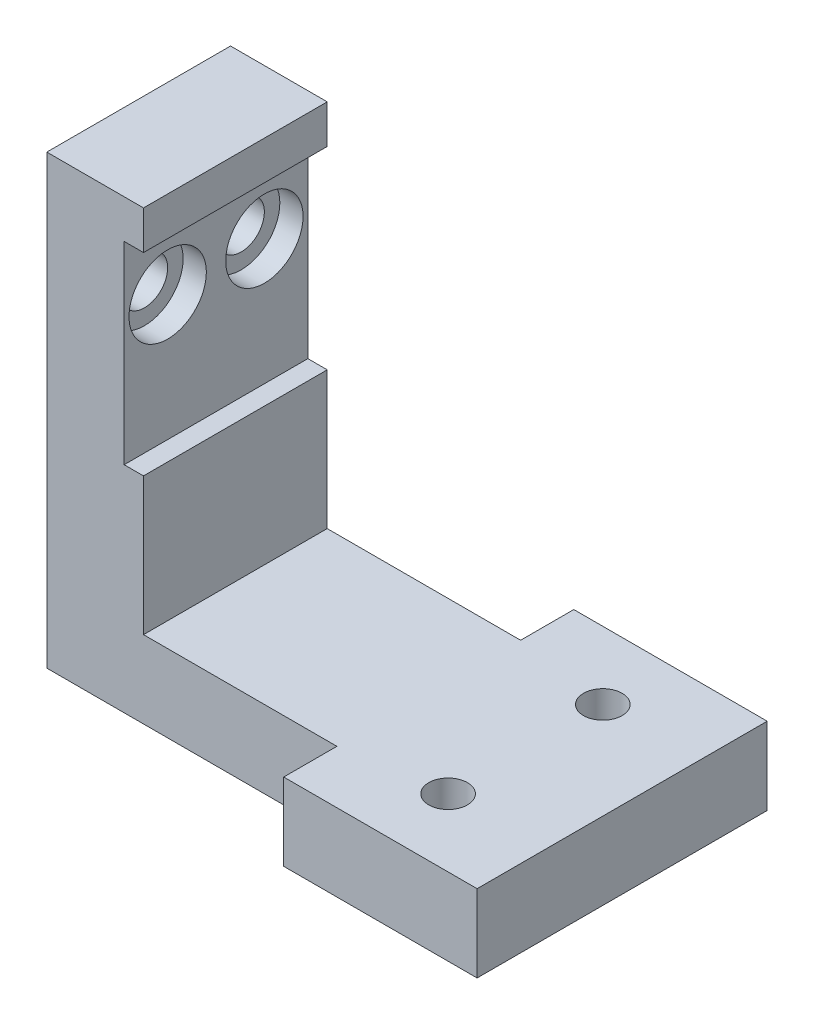
SolidWorks part; units mm, degrees
material "6061-T6 (SS)"
ref_plane "Front Plane" through (0, 0, 0) normal (0, 0, 1) x (1, 0, 0)
ref_plane "Top Plane" through (0, 0, 0) normal (0, 1, 0) x (1, 0, 0)
ref_plane "Right Plane" through (0, 0, 0) normal (1, 0, 0) x (0, 0, -1)
sketch "Sketch1" plane through (0, 0, 0) normal (0, 0, 1) x (1, 0, 0)
  line L0 (-15.4886, 8) -> (-17.5374, 8) construction
  line L9 (-17.5374, 3) -> (-17.5374, 13)
  line L10 (-21.5374, 0) -> (-21.5374, 15)
  line L11 (-21.5374, 15) -> (-16.5374, 15)
  line L12 (-16.5374, 15) -> (-16.5374, 13)
  line L17 (-12.4274, -4.11) -> (3.4626, -4.11)
  line L18 (3.4626, -4.11) -> (3.4626, -8.11)
  line L19 (3.4626, -8.11) -> (-13.4274, -8.11)
  line L20 (-17.5374, 13) -> (-16.5374, 13)
  line L21 (-17.5374, 3) -> (-16.5374, 3)
  line L22 (-16.5374, 3) -> (-16.5374, 0)
  line L23 (-21.5374, 0) -> (-21.5374, -8.11)
  line L24 (-21.5374, -8.11) -> (-13.4274, -8.11)
  line L25 (-16.5374, 0) -> (-16.5374, -4.11)
  line L26 (-16.5374, -4.11) -> (-12.4274, -4.11)
  line L29 (-12.4274, -4.11) -> (-10.0144, -4.11) construction
  point P15 (-17.5374, 8)
  point P21 (-12.4274, 0)
  dimension "D4" = 3
  dimension "D2" = 5
  dimension "D5" = 25
  dimension "D6" = 10
  dimension "D7" = 2
  dimension "D8" = 1
  dimension "D10" = 4
extrude "Boss-Extrude1" add sketch "Sketch1" along normal mid plane 9.5
sketch "Sketch2" plane through (-17.5374, 0, 0) normal (1, 0, 0) x (0, 0, -1)
  line L0 (-4.75, 8) -> (4.75, 8) construction
  line L1 (-4.75, 3) -> (-4.75, 13) construction
  line L2 (4.75, 3) -> (4.75, 13) construction
  line L3 (-4.75, 9.5) -> (4.75, 9.5) construction
  line L4 (0, 9.5) -> (0, 8) construction
  point P8 (-2.5, 9.5)
  point P11 (2.5, 9.5)
  dimension "D2" = 2.5
  dimension "D1" = 1.5
hole_wizard "M2 Clearance Hole1" positions "3DSketch1" profile "Sketch3" hole size "M2" standard "ANSI Metric" end condition through all
sketch3d "3DSketch1"
  point P0 (-17.5374, 9.5, 2.5)
  point P3 (-17.5374, 9.5, -2.5)
sketch "Sketch3" plane through (-17.5374, 9.5, 2.5) normal (0, 1, 0) x (0, 0, -1)
  line L0 (0, 0) -> (0, 4)
  line L1 (0, 4) -> (1.2, 4)
  line L2 (1.2, 4) -> (1.2, 0)
  line L5 (1.2, 0) -> (0, 0)
  line L11 (0, -6.35) -> (0, 107.95) construction
  dimension "Thru Hole Dia." = 2.4
  dimension "Thru Hole Depth" = 4
sketch "Sketch4" plane through (-17.5374, 0, 0) normal (1, 0, 0) x (0, 0, -1)
  circle A0 centre (-2.5, 9.5) radius 2
  circle A1 centre (2.5, 9.5) radius 2
  dimension "D1" = 4
  dimension "D2" = 4
extrude "Cut-Extrude1" cut sketch "Sketch4" against normal blind 1.2
sketch "Sketch5" plane through (0, -8.11, 0) normal (0, -1, 0) x (1, 0, 0)
  line L0 (3.4626, -7.5) -> (3.4626, 7.5)
  line L1 (3.4626, 4.75) -> (3.4626, -4.75) construction
  line L2 (3.4626, 7.5) -> (-6.5374, 7.5)
  line L3 (-6.5374, 7.5) -> (-6.5374, -7.5)
  line L4 (-6.5374, -7.5) -> (3.4626, -7.5)
  point P3 (3.4626, 0)
  dimension "D1" = 10
  dimension "D2" = 15
extrude "Boss-Extrude2" add sketch "Sketch5" against normal blind 4
sketch "Sketch6" plane through (0, -4.11, 0) normal (0, 1, 0) x (1, 0, 0)
  line L0 (3.4626, 0) -> (-6.5374, 0) construction
  line L1 (3.4626, 7.5) -> (3.4626, -7.5) construction
  line L3 (-1.5374, -7.5) -> (-1.5374, 7.5) construction
  line L4 (3.4626, -7.5) -> (-6.5374, -7.5) construction
  line L5 (-6.5374, 7.5) -> (3.4626, 7.5) construction
  point P12 (-1.5374, -4)
  point P13 (-1.5374, 0)
  point P14 (-1.5374, 4)
  dimension "D1" = 4
hole_wizard "Tap Drill for M2x0.4 Tap2" positions "3DSketch2" profile "Sketch7" hole size "M2x0.4" standard "ANSI Metric" end condition through all
sketch3d "3DSketch2"
  point P0 (-1.5374, -4.11, 4)
  point P3 (-1.5374, -4.11, -4)
sketch "Sketch7" plane through (-1.5374, -4.11, 4) normal (1, 0, 0) x (0, 0, 1)
  line L0 (0, 0) -> (0, 4)
  line L1 (0, 4) -> (1, 4)
  line L2 (1, 4) -> (1, 0)
  line L5 (1, 0) -> (0, 0)
  line L11 (0, -6.35) -> (0, 107.95) construction
  dimension "Thru Hole Dia." = 2
  dimension "Thru Hole Depth" = 4
